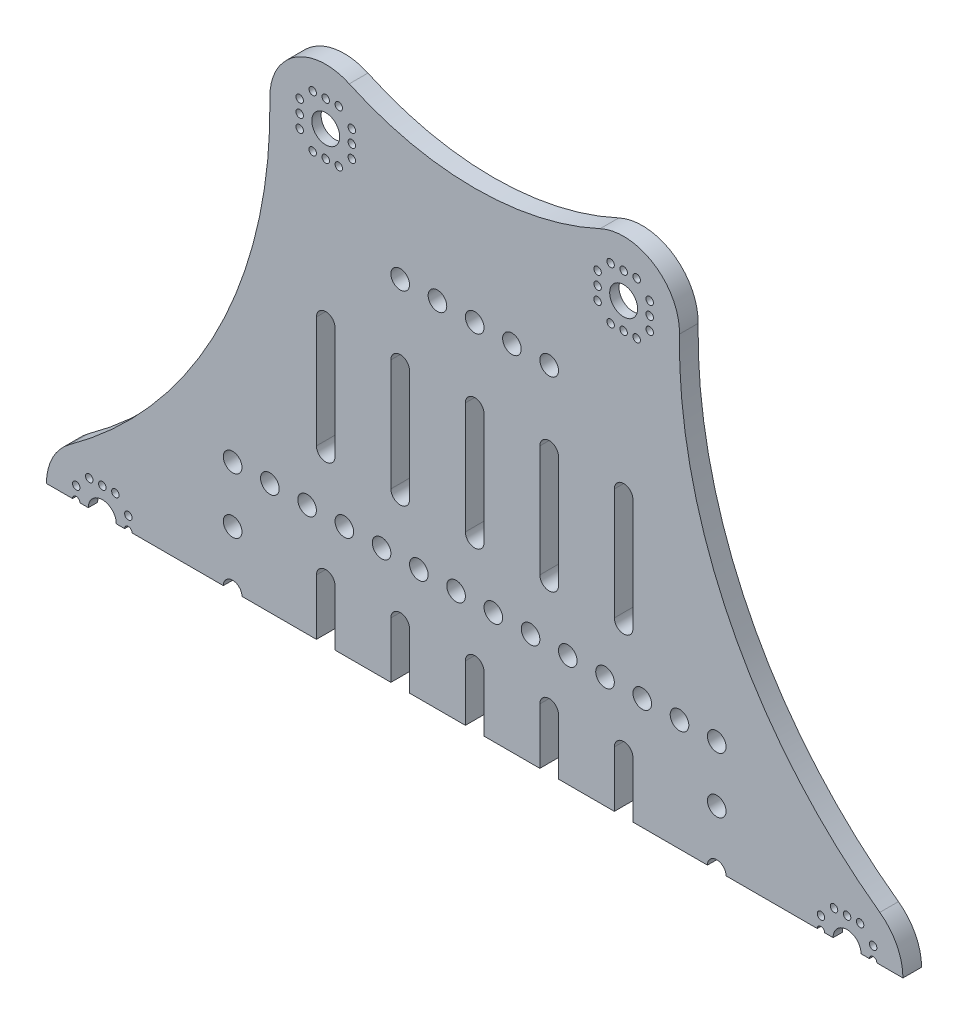
SolidWorks part; units mm, degrees
ref_plane "前视基准面" through (0, 0, 0) normal (0, 0, 1) x (1, 0, 0)
ref_plane "上视基准面" through (0, 0, 0) normal (0, 1, 0) x (1, 0, 0)
ref_plane "右视基准面" through (0, 0, 0) normal (1, 0, 0) x (0, 0, -1)
other "Configuration Table"
sketch "Sketch1" plane through (0, 0, 0) normal (0, 0, 1) x (1, 0, 0)
  line L0 (0, 0) -> (0, 120) construction
  line L1 (0, 120) -> (40, 120) construction
  line L2 (0, 0) -> (100, 0) construction
  circle A1 centre (100, 0) radius 15
  circle A2 centre (40, 120) radius 15
  circle A3 centre (-100, 0) radius 15
  circle A4 centre (-40, 120) radius 15
  circle A5 centre (40, -120) radius 15
  circle A6 centre (-40, -120) radius 15
  arc A7 (-33.6842, 133.6055) -> (33.6842, 133.6055) centre (0, 206.1684) ccw
  arc A8 (-33.6842, -133.6055) -> (33.6842, -133.6055) centre (0, -206.1684) cw
  arc A9 (-108.7909, 12.154) -> (-54.9978, 119.7403) centre (-184.9783, 117.4891) ccw
  arc A10 (108.7909, 12.154) -> (54.9978, 119.7403) centre (184.9783, 117.4891) cw
  arc A11 (108.7909, -12.154) -> (54.9978, -119.7403) centre (184.9783, -117.4891) ccw
  arc A12 (-108.7909, -12.154) -> (-54.9978, -119.7403) centre (-184.9783, -117.4891) cw
  dimension "D1" = 30
  dimension "D2" = 30
  dimension "D6" = 80
  dimension "D7" = 130
  dimension "D3" = 40
  dimension "D4" = 100
  dimension "D5" = 120
extrude "Boss-Extrude1" add sketch "Sketch1" along normal blind 5 contours A3 A12 A6 A8 A5 A11 A1 A10 A2 A7 A4 A9 | A3 | A4 | A2 | A1 | A5 | A6 A7 region at (100, 0, 0) region at (0, 0, 0) region at (40, 120, 0) region at (40, -120, 0) region at (-40, 120, 0) region at (-40, -120, 0) region at (-100, 0, 0)
sketch "Sketch2" plane through (0, 0, 0) normal (0, 0, -1) x (-1, 0, 0)
  line L0 (0, 0) -> (0, 91.5521) construction
  line L1 (0, 0) -> (39.9574, 0) construction
  circle A0 centre (-40, 120) radius 11.25
  circle A1 centre (-100, 0) radius 11.25
  circle A2 centre (100, 0) radius 11.25
  circle A3 centre (40, 120) radius 11.25
  circle A4 centre (40, -120) radius 11.25
  circle A5 centre (-40, -120) radius 11.25
  dimension "D1" = 22.5
extrude "Cut-Extrude1" cut sketch "Sketch2" against normal blind 2.5
sketch "Sketch3" plane through (0, 0, 2.5) normal (0, 0, -1) x (-1, 0, 0)
  line L0 (-40, 120) -> (-40, 127) construction
  line L1 (-40, 127) -> (-36.5, 127) construction
  line L2 (-100, 0) -> (-100, 7) construction
  line L3 (-100, 7) -> (-96.5, 7) construction
  circle A0 centre (-40, 120) radius 3.75
  circle A1 centre (-40, 127) radius 1
  circle A2 centre (-36.5, 127) radius 1
  circle A3 centre (-43.5, 127) radius 1
  circle A4 centre (-40, 120) radius 3.75
  circle A5 centre (-33, 123.5) radius 1
  circle A6 centre (-33, 120) radius 1
  circle A7 centre (-33, 116.5) radius 1
  circle A8 centre (-40, 120) radius 3.75
  circle A9 centre (-36.5, 113) radius 1
  circle A10 centre (-40, 113) radius 1
  circle A11 centre (-43.5, 113) radius 1
  circle A12 centre (-40, 120) radius 3.75
  circle A13 centre (-47, 116.5) radius 1
  circle A14 centre (-47, 120) radius 1
  circle A15 centre (-47, 123.5) radius 1
  circle A16 centre (-100, 0) radius 3.75
  circle A17 centre (-100, 7) radius 1
  circle A18 centre (-96.5, 7) radius 1
  circle A19 centre (-103.5, 7) radius 1
  circle A41 centre (-100, 0) radius 3.75
  circle A42 centre (-93, 3.5) radius 1
  circle A43 centre (-93, 0) radius 1
  circle A44 centre (-93, -3.5) radius 1
  circle A45 centre (-100, 0) radius 3.75
  circle A46 centre (-96.5, -7) radius 1
  circle A47 centre (-100, -7) radius 1
  circle A48 centre (-103.5, -7) radius 1
  circle A49 centre (-100, 0) radius 3.75
  circle A50 centre (-107, -3.5) radius 1
  circle A51 centre (-107, 0) radius 1
  circle A52 centre (-107, 3.5) radius 1
  point P33 (-40, 120)
  point P63 (-100, 0)
  dimension "D1" = 7.5
  dimension "D2" = 2
  dimension "D4" = 2
  dimension "D7" = 7.5
  dimension "D8" = 2
  dimension "D10" = 2
  dimension "D3" = 7
  dimension "D5" = 3.5
  dimension "D9" = 7
  dimension "D11" = 3.5
  dimension "D12" = 4
  dimension "D6" = 4
extrude "Cut-Extrude2" cut sketch "Sketch3" against normal blind 2.5 contours A15 | A14 | A13 | A0 | A11 | A10 | A9 | A7 | A6 | A5 | A2 | A1 | A3 | A47 | A49 | A43 | A45 | A16 | A50 | A51 | A52 | A19 | A17 | A18 | A46 | A48 | A44 | A42
mirror "Mirror1" about plane through (0, 0, 0) normal (1, 0, 0) of "Cut-Extrude2"
mirror "Mirror2" about plane through (0, 0, 0) normal (0, 1, 0) of "Cut-Extrude2", "Mirror1"
sketch "Sketch4" plane through (0, 0, 5) normal (0, 0, 1) x (1, 0, 0)
  arc A24 (-83.8778, 0) -> (-30.4292, 105.6743) centre (-184.9783, 117.4891) ccw
  arc A25 (-30.4292, -105.6743) -> (-83.8778, 0) centre (-184.9783, -117.4891) ccw
  arc A26 (30.4292, -105.6743) -> (-30.4292, -105.6743) centre (0, -206.1684) ccw
  arc A27 (83.8778, 0) -> (30.4292, -105.6743) centre (184.9783, -117.4891) ccw
  arc A28 (30.4292, 105.6743) -> (83.8778, 0) centre (184.9783, 117.4891) ccw
  arc A29 (-30.4292, 105.6743) -> (30.4292, 105.6743) centre (0, 206.1684) ccw
  arc A30 (-83.8778, 0) -> (-30.4292, 105.6743) centre (-184.9783, 117.4891) ccw
  arc A31 (-30.4292, -105.6743) -> (-83.8778, 0) centre (-184.9783, -117.4891) ccw
  arc A32 (30.4292, -105.6743) -> (-30.4292, -105.6743) centre (0, -206.1684) ccw
  arc A33 (83.8778, 0) -> (30.4292, -105.6743) centre (184.9783, -117.4891) ccw
  arc A34 (30.4292, 105.6743) -> (83.8778, 0) centre (184.9783, 117.4891) ccw
  arc A35 (-30.4292, 105.6743) -> (30.4292, 105.6743) centre (0, 206.1684) ccw
  dimension "D1" = 25
extrude "Cut-Extrude3" [suppressed] cut sketch "Sketch4" against normal through all
fillet "Fillet1" [suppressed] radius 20
sketch "Sketch5" plane through (0, 0, 0) normal (0, 0, -1) x (-1, 0, 0)
  line L0 (0, 95) -> (0, 126.1684) construction
  line L1 (0, 95) -> (20, 95) construction
  line L2 (0, -95) -> (0, -126.1684) construction
  line L3 (0, 0) -> (50.0339, 0) construction
  line L5 (0, -95) -> (20, -95) construction
  circle A0 centre (20, 95) radius 2.5
  circle A1 centre (0, 95) radius 2.5
  circle A2 centre (10, 95) radius 2.5
  circle A17 centre (10, -95) radius 2.5
  circle A18 centre (0, -95) radius 2.5
  circle A19 centre (20, -95) radius 2.5
  arc A20 (-33.6842, 133.6055) -> (33.6842, 133.6055) centre (0, 206.1684) ccw construction
  circle A21 centre (-20, 95) radius 2.5
  circle A22 centre (-10, 95) radius 2.5
  arc A23 (33.6842, -133.6055) -> (-33.6842, -133.6055) centre (0, -206.1684) ccw construction
  circle A24 centre (-20, -95) radius 2.5
  circle A25 centre (-10, -95) radius 2.5
  dimension "D1" = 5
  dimension "D2" = 5
  dimension "D4" = 5
  dimension "D3" = 95
  dimension "D5" = 10
extrude "Cut-Extrude4" cut sketch "Sketch5" against normal blind 12.5
sketch "Sketch7" [suppressed] plane through (0, 0, 0) normal (0, 0, -1) x (-1, 0, 0)
  line L0 (-142.3284, 63.1511) -> (-138.4501, 72.3684) construction
  line L1 (-66.361, 51.7375) -> (-44.32, 39.8221) construction
  line L2 (-152.9421, 69.9963) -> (-131.7148, 56.3059) construction
  line L3 (-131.7148, 56.3059) -> (-142.3284, 63.1511) construction
  line L4 (-55.3405, 45.7798) -> (-52.1848, 55.2688) construction
  circle A6 centre (-142.3284, 63.1511) radius 2.5
  circle A7 centre (-138.4501, 72.3684) radius 2.5
  circle A8 centre (-134.5717, 81.5857) radius 2.5
  circle A9 centre (-142.3284, 63.1511) radius 2.5
  circle A10 centre (-146.2068, 53.9338) radius 2.5
  circle A11 centre (-150.0851, 44.7165) radius 2.5
  arc A12 (-95.3356, 10.8708) -> (-54.9908, 100.526) centre (-184.9108, 105.0849) ccw construction
  arc A13 (-70.9715, 0) -> (-31.105, 85.8815) centre (-184.9108, 105.0849) ccw construction
  circle A14 centre (-55.3405, 45.7798) radius 2.5
  circle A15 centre (-52.1848, 55.2688) radius 2.5
  circle A16 centre (-48.3064, 64.4861) radius 2.5
  circle A17 centre (-59.2189, 36.5625) radius 2.5
  circle A18 centre (-63.0972, 27.3452) radius 2.5
  dimension "D1" = 5
  dimension "D2" = 5
  dimension "D7" = 5
  dimension "D9" = 5
  dimension "D3" = 100
  dimension "D4" = 10
  dimension "D5" = 10
  dimension "D6" = 10
  dimension "D8" = 100
  dimension "D10" = 10
  dimension "D11" = 2
extrude "Cut-Extrude5" [suppressed] cut sketch "Sketch7" against normal blind 10 contours A14 | A17 | A18 | A16 | A15
sketch "Sketch8" plane through (0, 0, 5) normal (0, 0, 1) x (1, 0, 0)
  line L0 (0, 0) -> (0, 75) construction
  line L1 (0, 75) -> (40, 75) construction
  line L2 (40, 75) -> (40, 45) construction
  line L3 (42.5, 75) -> (42.5, 45)
  line L4 (37.5, 75) -> (37.5, 45)
  line L5 (20, 75) -> (20, 45) construction
  line L6 (22.5, 75) -> (22.5, 45)
  line L7 (17.5, 75) -> (17.5, 45)
  line L8 (0, 75) -> (0, 45) construction
  line L9 (2.5, 75) -> (2.5, 45)
  line L10 (-2.5, 75) -> (-2.5, 45)
  line L11 (-20, 75) -> (-20, 45) construction
  line L12 (-17.5, 75) -> (-17.5, 45)
  line L13 (-22.5, 75) -> (-22.5, 45)
  line L14 (-40, 75) -> (-40, 45) construction
  line L15 (-37.5, 75) -> (-37.5, 45)
  line L16 (-42.5, 75) -> (-42.5, 45)
  line L17 (40, 120) -> (0, 120) construction
  line L18 (0, 15) -> (40, 15) construction
  line L19 (40, 15) -> (40, -15) construction
  line L20 (42.5, 15) -> (42.5, -15)
  line L21 (37.5, 15) -> (37.5, -15)
  line L22 (20, 15) -> (20, -15) construction
  line L23 (22.5, 15) -> (22.5, -15)
  line L24 (17.5, 15) -> (17.5, -15)
  line L25 (0, 15) -> (0, -15) construction
  line L26 (2.5, 15) -> (2.5, -15)
  line L27 (-2.5, 15) -> (-2.5, -15)
  line L28 (-20, 15) -> (-20, -15) construction
  line L29 (-17.5, 15) -> (-17.5, -15)
  line L30 (-22.5, 15) -> (-22.5, -15)
  line L31 (-40, 15) -> (-40, -15) construction
  line L32 (-37.5, 15) -> (-37.5, -15)
  line L33 (-42.5, 15) -> (-42.5, -15)
  line L34 (0, -45) -> (40, -45) construction
  line L35 (40, -45) -> (40, -75) construction
  line L36 (42.5, -45) -> (42.5, -75)
  line L37 (37.5, -45) -> (37.5, -75)
  line L38 (20, -45) -> (20, -75) construction
  line L39 (22.5, -45) -> (22.5, -75)
  line L40 (17.5, -45) -> (17.5, -75)
  line L41 (0, -45) -> (0, -75) construction
  line L42 (2.5, -45) -> (2.5, -75)
  line L43 (-2.5, -45) -> (-2.5, -75)
  line L44 (-20, -45) -> (-20, -75) construction
  line L45 (-17.5, -45) -> (-17.5, -75)
  line L46 (-22.5, -45) -> (-22.5, -75)
  line L47 (-40, -45) -> (-40, -75) construction
  line L48 (-37.5, -45) -> (-37.5, -75)
  line L49 (-42.5, -45) -> (-42.5, -75)
  arc A0 (42.5, 75) -> (37.5, 75) centre (40, 75) ccw
  arc A1 (37.5, 45) -> (42.5, 45) centre (40, 45) ccw
  arc A2 (22.5, 75) -> (17.5, 75) centre (20, 75) ccw
  arc A3 (17.5, 45) -> (22.5, 45) centre (20, 45) ccw
  arc A4 (2.5, 75) -> (-2.5, 75) centre (0, 75) ccw
  arc A5 (-2.5, 45) -> (2.5, 45) centre (0, 45) ccw
  arc A6 (-17.5, 75) -> (-22.5, 75) centre (-20, 75) ccw
  arc A7 (-22.5, 45) -> (-17.5, 45) centre (-20, 45) ccw
  arc A8 (-37.5, 75) -> (-42.5, 75) centre (-40, 75) ccw
  arc A9 (-42.5, 45) -> (-37.5, 45) centre (-40, 45) ccw
  arc A10 (42.5, 15) -> (37.5, 15) centre (40, 15) ccw
  arc A11 (37.5, -15) -> (42.5, -15) centre (40, -15) ccw
  arc A12 (22.5, 15) -> (17.5, 15) centre (20, 15) ccw
  arc A13 (17.5, -15) -> (22.5, -15) centre (20, -15) ccw
  arc A14 (2.5, 15) -> (-2.5, 15) centre (0, 15) ccw
  arc A15 (-2.5, -15) -> (2.5, -15) centre (0, -15) ccw
  arc A16 (-17.5, 15) -> (-22.5, 15) centre (-20, 15) ccw
  arc A17 (-22.5, -15) -> (-17.5, -15) centre (-20, -15) ccw
  arc A18 (-37.5, 15) -> (-42.5, 15) centre (-40, 15) ccw
  arc A19 (-42.5, -15) -> (-37.5, -15) centre (-40, -15) ccw
  arc A20 (42.5, -45) -> (37.5, -45) centre (40, -45) ccw
  arc A21 (37.5, -75) -> (42.5, -75) centre (40, -75) ccw
  arc A22 (22.5, -45) -> (17.5, -45) centre (20, -45) ccw
  arc A23 (17.5, -75) -> (22.5, -75) centre (20, -75) ccw
  arc A24 (2.5, -45) -> (-2.5, -45) centre (0, -45) ccw
  arc A25 (-2.5, -75) -> (2.5, -75) centre (0, -75) ccw
  arc A26 (-17.5, -45) -> (-22.5, -45) centre (-20, -45) ccw
  arc A27 (-22.5, -75) -> (-17.5, -75) centre (-20, -75) ccw
  arc A28 (-37.5, -45) -> (-42.5, -45) centre (-40, -45) ccw
  arc A29 (-42.5, -75) -> (-37.5, -75) centre (-40, -75) ccw
  point P3 (40, 60)
  point P11 (20, 60)
  point P18 (0, 60)
  point P25 (-20, 60)
  point P32 (-40, 60)
  point P44 (40, 0)
  point P51 (20, 0)
  point P58 (0, 0)
  point P65 (-20, 0)
  point P72 (-40, 0)
  point P80 (40, -60)
  point P87 (20, -60)
  point P94 (0, -60)
  point P101 (-20, -60)
  point P108 (-40, -60)
  dimension "D3" = 2.5
  dimension "D1" = 40
  dimension "D2" = 75
  dimension "D4" = 30
  dimension "D6" = 20
  dimension "D8" = 60
  dimension "D5" = 5
  dimension "D7" = 3
extrude "Cut-Extrude6" cut sketch "Sketch8" against normal blind 10
sketch "Sketch9" plane through (0, 0, 5) normal (0, 0, 1) x (1, 0, 0)
  line L0 (0, 0) -> (0, 30) construction
  line L1 (0, 30) -> (-65, 30) construction
  line L2 (0, 0) -> (100, 0) construction
  line L3 (0, -30) -> (-65, -30) construction
  circle A0 centre (-65, 30) radius 2.5
  circle A1 centre (-55, 30) radius 2.5
  circle A2 centre (-45, 30) radius 2.5
  circle A3 centre (-35, 30) radius 2.5
  circle A4 centre (-25, 30) radius 2.5
  circle A5 centre (-15, 30) radius 2.5
  circle A6 centre (-5, 30) radius 2.5
  circle A7 centre (5, 30) radius 2.5
  circle A8 centre (15, 30) radius 2.5
  circle A9 centre (25, 30) radius 2.5
  circle A10 centre (35, 30) radius 2.5
  circle A11 centre (45, 30) radius 2.5
  circle A12 centre (55, 30) radius 2.5
  circle A13 centre (65, 30) radius 2.5
  circle A14 centre (65, -30) radius 2.5
  circle A15 centre (55, -30) radius 2.5
  circle A16 centre (45, -30) radius 2.5
  circle A17 centre (35, -30) radius 2.5
  circle A18 centre (25, -30) radius 2.5
  circle A19 centre (15, -30) radius 2.5
  circle A20 centre (5, -30) radius 2.5
  circle A21 centre (-5, -30) radius 2.5
  circle A22 centre (-15, -30) radius 2.5
  circle A23 centre (-25, -30) radius 2.5
  circle A24 centre (-35, -30) radius 2.5
  circle A25 centre (-45, -30) radius 2.5
  circle A26 centre (-55, -30) radius 2.5
  circle A27 centre (-65, -30) radius 2.5
  dimension "D1" = 5
  dimension "D2" = 30
  dimension "D3" = 65
  dimension "D5" = 10
  dimension "D4" = 14
extrude "Cut-Extrude7" cut sketch "Sketch9" against normal blind 10
sketch "Sketch10" plane through (0, 0, 5) normal (0, 0, 1) x (1, 0, 0)
  line L0 (0, 0) -> (-65, 0) construction
  line L1 (-65, 0) -> (-40, 15) construction
  line L2 (-40, 15) -> (-65, 15) construction
  line L3 (-65, 15) -> (-65, 0) construction
  line L4 (0, 0) -> (0, 17.5) construction
  circle A1 centre (-65, 0) radius 2.5
  circle A2 centre (-65, 15) radius 2.5
  circle A3 centre (-65, -15) radius 2.5
  arc A4 (2.5, 15) -> (-2.5, 15) centre (0, 15) ccw construction
  circle A5 centre (65, -15) radius 2.5
  circle A6 centre (65, 0) radius 2.5
  circle A7 centre (65, 15) radius 2.5
  dimension "D1" = 5
  dimension "D3" = 5
  dimension "D2" = 65
extrude "Cut-Extrude8" cut sketch "Sketch10" against normal blind 10
sketch "Sketch11" plane through (0, 0, 5) normal (0, 0, 1) x (1, 0, 0)
  line L0 (-115, 0) -> (115, 0)
  line L1 (-115, -135) -> (115, -135)
  line L2 (-115, -135) -> (-115, 135)
  line L3 (-115, 135) -> (115, 135)
  line L4 (115, -135) -> (115, 135)
  line L5 (-115, -135) -> (115, 135) construction
  line L6 (-115, 135) -> (115, -135) construction
  point P0 (0, 0)
  dimension "D1" = 270
  dimension "D2" = 230
extrude "Cut-Extrude9" cut sketch "Sketch11" against normal blind 10 contours L1 L4 L0 L2 region at (0, -67.5, 5)
